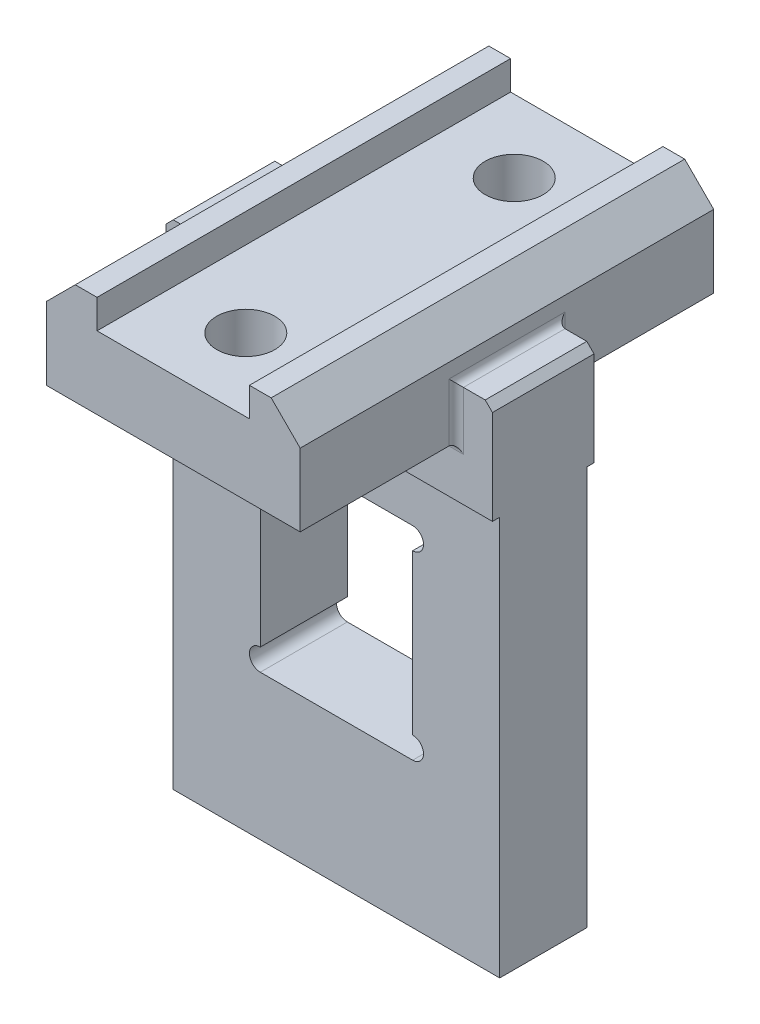
SolidWorks part; units mm, degrees
ref_plane "정면" through (0, 0, 0) normal (0, 0, 1) x (1, 0, 0)
ref_plane "윗면" through (0, 0, 0) normal (0, 1, 0) x (1, 0, 0)
ref_plane "우측면" through (0, 0, 0) normal (1, 0, 0) x (0, 0, -1)
sketch "스케치2" plane through (0, 0, 0) normal (0, 0, 1) x (1, 0, 0)
  line L0 (0, 0) -> (0, 76) construction
  line L1 (-22.5, 55) -> (22.5, 55)
  line L2 (-22.5, 55) -> (-22.5, 0)
  line L3 (-22.5, 0) -> (22.5, 0)
  line L4 (22.5, 55) -> (22.5, 0)
  line L9 (-22.5, 69) -> (22.5, 69)
  line L10 (-22.5, 69) -> (-22.5, 55)
  line L11 (-22.5, 55) -> (22.5, 55)
  line L12 (22.5, 69) -> (22.5, 55)
  line L13 (-17.5, 76) -> (17.5, 76)
  line L14 (-17.5, 76) -> (-17.5, 62)
  line L15 (-17.5, 62) -> (17.5, 62)
  line L16 (17.5, 76) -> (17.5, 62)
  line L17 (-10.5, 76) -> (10.5, 76)
  line L18 (-10.5, 76) -> (-10.5, 72)
  line L19 (-10.5, 72) -> (10.5, 72)
  line L20 (10.5, 76) -> (10.5, 72)
  line L22 (-10.5, 48) -> (10.5, 48)
  line L23 (-10.5, 48) -> (-10.5, 20)
  line L24 (-10.5, 20) -> (10.5, 20)
  line L25 (10.5, 48) -> (10.5, 20)
  circle A0 centre (-10.5, 46.5) radius 1.5
  circle A1 centre (-10.5, 21.5) radius 1.5
  circle A2 centre (10.5, 21.5) radius 1.5
  circle A3 centre (10.5, 46.5) radius 1.5
  point P29 (0, 0)
  point P30 (0, 0)
  dimension "D11" = 3
  dimension "D1" = 76
  dimension "D2" = 55
  dimension "D3" = 69
  dimension "D4" = 45
  dimension "D5" = 14
  dimension "D6" = 21
  dimension "D7" = 35
  dimension "D8" = 4
  dimension "D9" = 28
  dimension "D10" = 20
sketch "스케치3" plane through (0, 0, 0) normal (0, 0, 1) x (1, 0, 0)
extrude "보스-돌출1" add sketch "스케치2" along normal mid plane 12 contours L3 L0 L24 A1 L23 A0 L22 L1 L2 | L0 L3 L4 L11 L22 A3 L25 A2 L24 region at (-13.1346, 25.4102, 0) region at (13.1346, 25.4102, 0)
extrude "보스-돌출2" add sketch "스케치2<5>" along normal mid plane 14 contours L1 L0 L15 L14 L9 L10 | L0 L11 L12 L9 L16 L15 region at (-12.8409, 59.7727, 0) region at (12.8409, 59.7727, 0)
sketch "스케치2<5>" plane through (0, 0, 0) normal (0, 0, 1) x (1, 0, 0) same geometry as "스케치2"
extrude "보스-돌출3" add sketch "스케치2<6>" along normal mid plane 57 contours L15 L0 L9 L14 | L0 L15 L16 L9 | L0 L9 L16 L13 L20 L19 | L9 L0 L19 L18 L13 L14 region at (-8.75, 65.5, 0) region at (8.75, 65.5, 0) region at (-10.5761, 71.7174, 0) region at (10.5761, 71.7174, 0)
sketch "스케치2<6>" plane through (0, 0, 0) normal (0, 0, 1) x (1, 0, 0) same geometry as "스케치2"
chamfer "모따기1" distance 4 angle 45 2 edges at (17.5, 76, 0) (-17.5, 76, 0)
hole_wizard "구멍1" positions "스케치4" profile "스케치5" legacy end condition through all
sketch "스케치4" plane through (0, 72, 0) normal (0, 1, 0) x (1, 0, 0)
  line L0 (-10.5, 28.5) -> (10.5, 28.5) construction
  point P0 (0, 18.5)
  point P2 (0, -18.5)
  point P5 (0, 0)
  dimension "D1" = 10
  dimension "D2" = 37
sketch "스케치5" plane through (0, 72, -18.5) normal (1, 0, 0) x (0, 0, 1)
  line L0 (0, 0) -> (0, 72)
  line L1 (0, 72) -> (4, 72)
  line L2 (4, 72) -> (4, 0)
  line L3 (4, 0) -> (0, 0)
  line L4 (0, 110) -> (0, -10) construction
  dimension "지름" = 8
  dimension "깊이" = 72
fillet "필렛1" radius 1 8 edges at (0, 62, 7) (-17.5, 65.5, 7) (-17.5, 69, 0) (-17.5, 65.5, -7) (0, 62, -7) (17.5, 65.5, -7) (17.5, 65.5, 7) (17.5, 69, 0)
chamfer "모따기2" distance 1 angle 45 2 edges at (-22.5, 69, 0) (22.5, 69, 0)
